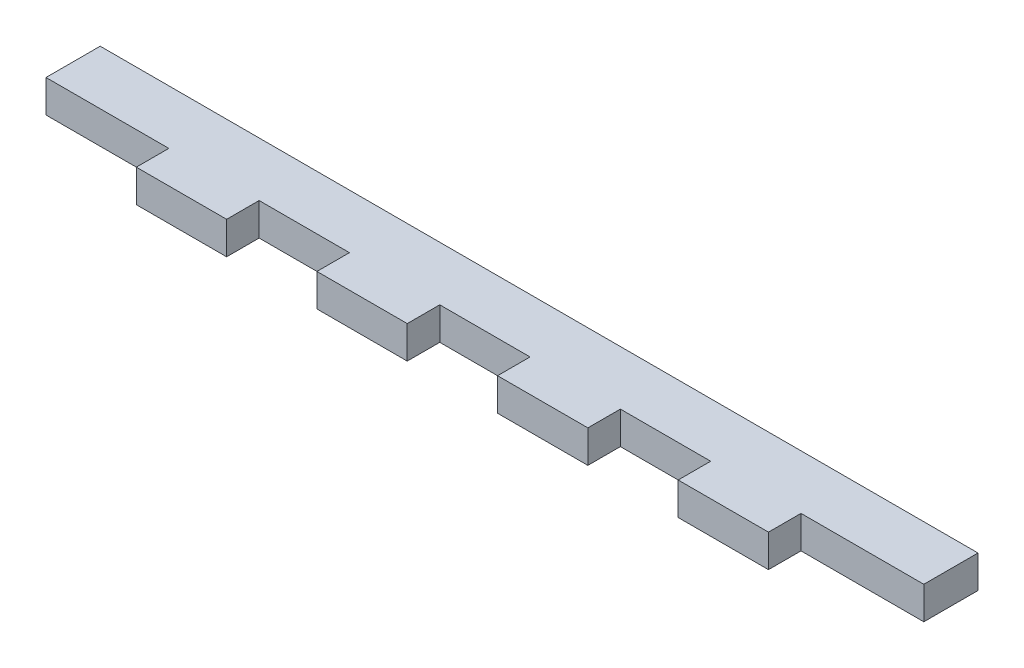
SolidWorks part; units mm, degrees
ref_plane "Front Plane" through (0, 0, 0) normal (0, 0, 1) x (1, 0, 0)
ref_plane "Top Plane" through (0, 0, 0) normal (0, 1, 0) x (1, 0, 0)
ref_plane "Right Plane" through (0, 0, 0) normal (1, 0, 0) x (0, 0, -1)
sketch "Sketch1" plane through (0, 0, 0) normal (0, 1, 0) x (1, 0, 0)
  line L1 (-81, 5) -> (81, 5)
  line L2 (-81, 5) -> (-81, -5)
  line L3 (-81, -5) -> (81, -5)
  line L4 (81, 5) -> (81, -5)
  line L5 (-81, 5) -> (81, -5) construction
  line L6 (-81, -5) -> (81, 5) construction
  point P0 (0, 0)
  dimension "D1" = 162
  dimension "D2" = 10
sketch "Sketch2" plane through (0, 0, 0) normal (0, 0, 1) x (1, 0, 0)
  line L0 (0, 0) -> (0, 6) construction
  line L1 (-81, 0) -> (81, 0) construction
extrude "Boss-Extrude1" add sketch "Sketch1" along normal up to vertex (6 mm away) contours L2 L3 L4 L1 up to point (0, 6, 0)
sketch "Sketch4" plane through (0, 0, 0) normal (0, -1, 0) x (1, 0, 0)
  line L0 (0, 0) -> (0, 11)
  line L1 (8.3333, 11) -> (-8.3333, 11)
  line L3 (-75, 11) -> (-58.3333, 11) construction
  line L4 (-81, 5) -> (81, 5) construction
  line L5 (-8.3333, 11) -> (-25, 11)
  line L6 (-8.3333, 11) -> (-8.3333, 5)
  line L7 (-8.3333, 5) -> (-25, 5)
  line L8 (-25, 11) -> (-25, 5)
  line L9 (-58.3333, 11) -> (-75, 11)
  line L10 (-25, 5) -> (-41.6667, 5)
  line L11 (-25, 5) -> (-25, 11)
  line L12 (-25, 11) -> (-41.6667, 11)
  line L13 (-41.6667, 5) -> (-41.6667, 11)
  line L14 (-41.6667, 11) -> (-58.3333, 11)
  line L15 (-41.6667, 11) -> (-41.6667, 5)
  line L16 (-41.6667, 5) -> (-58.3333, 5)
  line L17 (-58.3333, 11) -> (-58.3333, 5)
  point P9 (0, 11)
  point P19 (-20.7615, 11)
  point P20 (-41.9987, 11)
  point P22 (-53.7018, 5)
  line M17 (81, 5) -> (-81, 5)
extrude "Boss-Extrude3" add sketch "Sketch4" against normal up to surface (6 mm away) contours L5 L8 L6 M17 | L14 L17 L13 M17 region at (-16.6667, 0, 8) region at (-50, 0, 8) up to face at (0, 6, 0)
mirror "Mirror1" about plane through (0, 0, 0) normal (1, 0, 0) of "Boss-Extrude3"
equation "\"glass_width\"= 150"
equation "\"glass_height\"= 100"
equation "\"glass_thickness\"= 4"
equation "\"brood_space\"= 42"
equation "\"t1\"= 6"
equation "\"t2\"= 6"
equation "\"box_depth\"= \"brood_space\" + \"glass_thickness\" + \"glass_thickness\" + \"t2\" + \"t2\""
equation "\"box_width\"= \"glass_width\" + \"t1\" + \"t1\""
equation "\"food_height\"= 70"
equation "\"box_height\"= \"glass_height\" + ( \"t1\" * 3 ) + \"food_height\""
equation "\"D1@Sketch1\"=\"box_width\""
equation "\"D1@Sketch2\"=\"t2\""
equation "\"entry_height\"= 24"
equation "\"entry_diameter\"= 8"
equation "\"food_top_clearance\"= 10"
equation "\"bar_width\"= 20"
equation "\"glassblocker_lower_height\"= 10"
equation "\"lower_edge_stickout\"=6"
